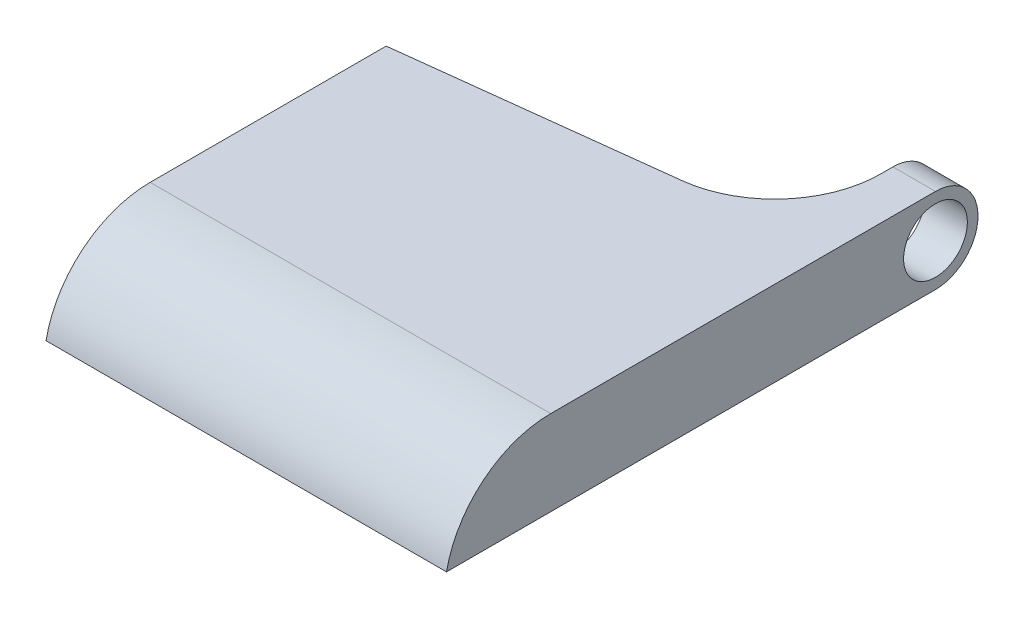
SolidWorks part; units mm, degrees
material "Nickel"
ref_plane "Front Plane" through (0, 0, 0) normal (0, 0, 1) x (1, 0, 0)
ref_plane "Top Plane" through (0, 0, 0) normal (0, 1, 0) x (1, 0, 0)
ref_plane "Right Plane" through (0, 0, 0) normal (1, 0, 0) x (0, 0, -1)
sketch "Sketch2" plane through (0, 0, 0) normal (0, 1, 0) x (1, 0, 0)
  line L0 (0, 0) -> (18.84, 0)
  line L1 (18.84, 0) -> (18.84, 25)
  line L2 (18.84, 25) -> (16.84, 25)
  line L3 (16.84, 25) -> (16.84, 18)
  line L4 (16.84, 18) -> (0, 16)
  line L5 (0, 16) -> (0, 0)
  dimension "D1" = 25
  dimension "D2" = 18.84
  dimension "D3" = 2
  dimension "D4" = 7
  dimension "D5" = 16
extrude "Boss-Extrude1" add sketch "Sketch2" along normal blind 4
fillet "Fillet1" radius 5 1 edges at (9.42, 4, 0)
fillet "Fillet2" radius 5 1 edges at (16.84, 2, -18)
ref_plane "Plane1" through (0, -3, 0) normal (0, 1, 0) x (1, 0, 0)
sketch "Sketch3" plane through (0, -3, 0) normal (0, 1, 0) x (1, 0, 0)
  line L0 (18.84, 10.332) -> (0, 10.332) construction
  line L1 (18.84, 4.899) -> (18.84, 25) construction
  line L2 (0, 16) -> (0, 4.899) construction
  line L3 (9.42, 4.899) -> (9.42, 10.332) construction
  line L4 (0, 4.899) -> (18.84, 4.899) construction
  circle A0 centre (9.42, 10.332) radius 0.1001
  dimension "D1" = 0.2002
sketch "Sketch4" plane through (0, 0, 0) normal (0, -1, 0) x (1, 0, 0)
  line L0 (18.84, 0) -> (18.84, -25) construction
  line L1 (0, 0) -> (18.84, 0)
  line L2 (0, 0) -> (0, -16)
  line L3 (0, -16) -> (18.84, -16)
  line L4 (18.84, 0) -> (18.84, -16)
loft "Loft2" [suppressed] add profiles "Sketch3", "Sketch4"
sketch "Sketch6" plane through (18.84, 0, 0) normal (1, 0, 0) x (0, 0, -1)
  line L0 (4.899, 4) -> (25, 4) construction
  line L1 (25, 4) -> (25, 0) construction
  line L3 (20.4947, 4) -> (25, 4)
  line L4 (20.4947, 4) -> (20.4947, 0)
  line L5 (20.4947, 0) -> (25, 0)
  line L6 (25, 4) -> (25, 0)
  circle A0 centre (23, 2) radius 1.5
  circle A1 centre (23, 2) radius 2
  line M3 (25, 4) -> (4.899, 4)
  line M7 (25, 0) -> (25, 4)
  dimension "D1" = 3
  dimension "D2" = 4
extrude "Cut-Extrude1" cut sketch "Sketch6" against normal through all contours A0 | A1 L6 M3 | A1 L5 M7 region at (18.84, 3.5533, -24.5533) region at (18.84, 0.4467, -24.5533) region at (18.84, 2, -23)
